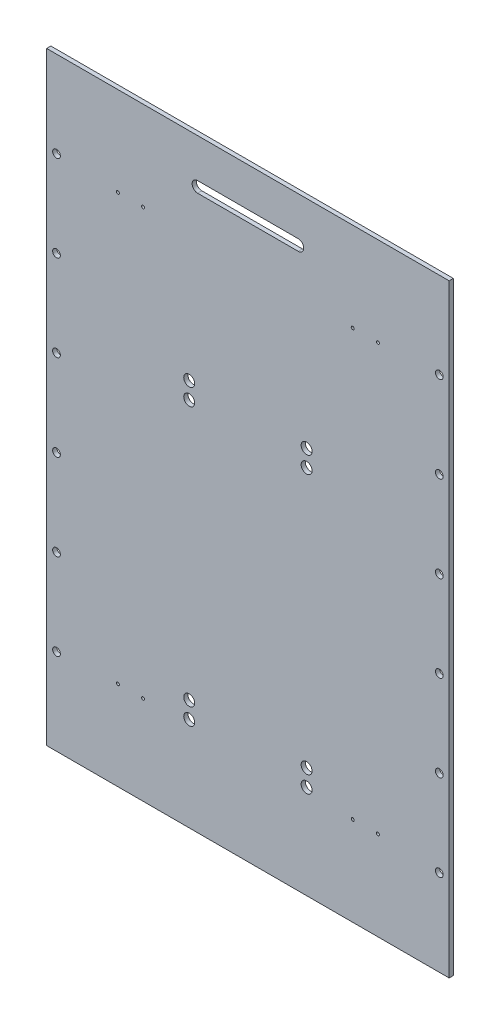
SolidWorks part; units mm, degrees
material "Plain Carbon Steel"
ref_plane "Front Plane" through (0, 0, 0) normal (0, 0, 1) x (1, 0, 0)
ref_plane "Top Plane" through (0, 0, 0) normal (0, 1, 0) x (1, 0, 0)
ref_plane "Right Plane" through (0, 0, 0) normal (1, 0, 0) x (0, 0, -1)
sketch "Sketch1" plane through (0, 0, 0) normal (0, 0, 1) x (1, 0, 0)
  line L1 (-304.8, -457.2) -> (304.8, -457.2)
  line L2 (-304.8, -457.2) -> (-304.8, 457.2)
  line L3 (-304.8, 457.2) -> (304.8, 457.2)
  line L4 (304.8, -457.2) -> (304.8, 457.2)
  line L5 (-304.8, -457.2) -> (304.8, 457.2) construction
  line L6 (-304.8, 457.2) -> (304.8, -457.2) construction
  point P0 (0, 0)
  dimension "D1" = 914.4
  dimension "D2" = 609.6
extrude "Boss-Extrude1" add sketch "Sketch1" along normal mid plane 6.35
sketch "Sketch2" plane through (0, 0, 3.175) normal (0, 0, 1) x (1, 0, 0)
  line L0 (-304.8, -457.2) -> (304.8, -457.2) construction
  line L1 (-304.8, 457.2) -> (-304.8, -457.2) construction
  line L2 (0, 457.2) -> (0, -457.2) construction
  line L3 (304.8, 457.2) -> (-304.8, 457.2) construction
  line L4 (304.8, 0) -> (-304.8, 0) construction
  line L5 (304.8, -457.2) -> (304.8, 457.2) construction
  point P0 (-196.85, -322.2625)
  point P1 (-158.75, -322.2625)
  point P14 (196.85, -322.2625)
  point P15 (158.75, -322.2625)
  point P16 (158.75, 322.2625)
  point P17 (196.85, 322.2625)
  point P18 (-158.75, 322.2625)
  point P19 (-196.85, 322.2625)
  dimension "D1" = 134.9375
  dimension "D2" = 107.95
  dimension "D3" = 38.1
hole_wizard "#8 Clearance Hole1" positions "Sketch2" profile "Sketch3" hole size "#8" standard "ANSI Inch" end condition up to next
sketch "Sketch3" plane through (-196.85, -322.2625, 3.175) normal (1, 0, 0) x (0, -1, 0)
  line L0 (0, 0) -> (0, 6.35)
  line L1 (0, 6.35) -> (2.2479, 6.35)
  line L2 (2.2479, 6.35) -> (2.2479, 0)
  line L5 (2.2479, 0) -> (0, 0)
  line L11 (0, -6.35) -> (0, 107.95) construction
  dimension "Thru Hole Dia." = 4.4958
  dimension "Thru Hole Depth" = 6.35
sketch "Sketch4" plane through (0, 0, 3.175) normal (0, 0, 1) x (1, 0, 0)
  line L0 (0, 457.2) -> (0, -457.2) construction
  line L1 (304.8, 457.2) -> (-304.8, 457.2) construction
  line L2 (-304.8, -457.2) -> (304.8, -457.2) construction
  line L3 (-88.9, 129.5426) -> (-88.9, 104.1426) construction
  line L4 (-76.2, 389.8926) -> (76.2, 389.8926) construction
  line L5 (-76.2, 398.1629) -> (76.2, 398.1629)
  line L6 (-76.2, 381.6224) -> (76.2, 381.6224)
  circle A0 centre (76.2, 389.8926) radius 6.7462 construction
  circle A1 centre (76.2, 389.8926) radius 6.7462 construction
  circle A2 centre (-25.4, 389.8926) radius 6.7462 construction
  circle A3 centre (25.4, 389.8926) radius 6.7462 construction
  circle A4 centre (-76.2, 389.8926) radius 6.7462 construction
  circle A5 centre (-25.4, 389.8926) radius 6.7462 construction
  circle A6 centre (25.4, 389.8926) radius 6.7462 construction
  circle A7 centre (-76.2, 389.8926) radius 6.7462 construction
  circle A8 centre (76.2, 389.8926) radius 8.2702
  circle A9 centre (-25.4, 389.8926) radius 8.2702
  circle A10 centre (25.4, 389.8926) radius 8.2702
  circle A11 centre (-76.2, 389.8926) radius 8.2702
  circle A12 centre (-88.9, 129.5426) radius 8.2702
  circle A13 centre (-88.9, 104.1426) radius 8.2702
  circle A14 centre (-88.9, -289.5574) radius 8.2702
  circle A15 centre (-88.9, -314.9574) radius 8.2702
  circle A16 centre (88.9, -314.9574) radius 8.2702
  circle A17 centre (88.9, -289.5574) radius 8.2702
  circle A18 centre (88.9, 104.1426) radius 8.2702
  circle A19 centre (88.9, 129.5426) radius 8.2702
  arc A20 (-76.2, 398.1629) -> (-76.2, 381.6224) centre (-76.2, 389.8926) ccw
  arc A21 (76.2, 381.6224) -> (76.2, 398.1629) centre (76.2, 389.8926) ccw
  point P34 (0, 389.8926)
  dimension "D3" = 88.9
  dimension "D2" = 25.4
  dimension "D4" = 260.35
  dimension "D5" = 679.45
  dimension "D6" = 25.4
  dimension "D1" = 1.524
extrude "Cut-Extrude1" cut sketch "Sketch4" against normal through all both and the other way through all contours L5 A21 L6 A20 | A12 | A13 | A19 | A18 | A14 | A15 | A17 | A16
sketch "Sketch8" plane through (0, 0, 3.175) normal (0, 0, 1) x (1, 0, 0)
  line L0 (-304.8, 457.2) -> (-304.8, -457.2) construction
  line L1 (-304.8, -457.2) -> (304.8, -457.2) construction
  line L2 (0, 457.2) -> (0, -457.2) construction
  line L3 (304.8, 457.2) -> (-304.8, 457.2) construction
  circle A0 centre (158.75, -322.2625) radius 2.2479 construction
  point P0 (-289.8775, -326.5714)
  point P7 (-289.8775, -195.9429)
  point P8 (-289.8775, -65.3143)
  point P9 (-289.8775, 65.3143)
  point P10 (-289.8775, 195.9429)
  point P11 (-289.8775, 326.5714)
  point P17 (289.8775, 326.5714)
  point P18 (289.8775, 195.9429)
  point P19 (289.8775, 65.3143)
  point P20 (289.8775, -65.3143)
  point P21 (289.8775, -195.9429)
  point P22 (289.8775, -326.5714)
  dimension "D1" = 14.9225
  dimension "D2" = 130.6286
  dimension "D4" = 126.3196
  dimension "D3" = 6
hole_wizard "3/8 Clearance Hole1" positions "Sketch8" profile "Sketch9" hole size "3/8" standard "ANSI Inch" end condition up to next
sketch "Sketch9" plane through (-289.8775, -326.5714, 3.175) normal (1, 0, 0) x (0, -1, 0)
  line L0 (0, 0) -> (0, 6.35)
  line L1 (0, 6.35) -> (5.842, 6.35)
  line L2 (5.842, 6.35) -> (5.842, 0)
  line L5 (5.842, 0) -> (0, 0)
  line L11 (0, -6.35) -> (0, 107.95) construction
  dimension "Thru Hole Dia." = 11.684
  dimension "Thru Hole Depth" = 6.35
